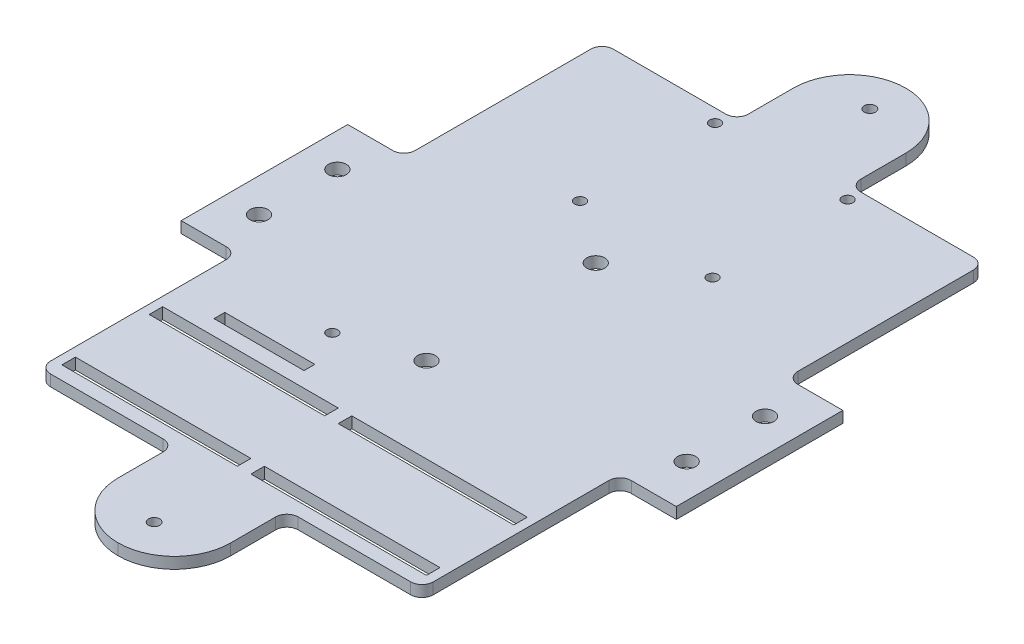
SolidWorks part; units mm, degrees
ref_plane "Front Plane" through (0, 0, 0) normal (0, 0, 1) x (1, 0, 0)
ref_plane "Top Plane" through (0, 0, 0) normal (0, 1, 0) x (1, 0, 0)
ref_plane "Right Plane" through (0, 0, 0) normal (1, 0, 0) x (0, 0, -1)
sketch "Sketch1" plane through (0, 0, 0) normal (0, 1, 0) x (1, 0, 0)
  line L0 (0, 102.87) -> (0, 158.75)
  line L1 (0, 0) -> (38.1, 0)
  line L2 (0, 0) -> (0, 55.88)
  line L3 (0, 158.75) -> (38.1, 158.75)
  line L4 (107.95, 0) -> (107.95, 55.88)
  line L5 (0, 102.87) -> (-15.875, 102.87)
  line L7 (0, 55.88) -> (-15.875, 55.88)
  line L8 (-15.875, 102.87) -> (-15.875, 55.88)
  line L9 (107.95, 102.87) -> (123.825, 102.87)
  line L11 (107.95, 55.88) -> (123.825, 55.88)
  line L12 (123.825, 102.87) -> (123.825, 55.88)
  line L14 (38.1, 158.75) -> (38.1, 190.5)
  line L15 (38.1, 190.5) -> (69.85, 190.5)
  line L16 (69.85, 158.75) -> (69.85, 190.5)
  line L18 (38.1, 0) -> (38.1, -31.75)
  line L19 (38.1, -31.75) -> (69.85, -31.75)
  line L20 (69.85, 0) -> (69.85, -31.75)
  line L21 (69.85, 158.75) -> (107.95, 158.75)
  line L22 (107.95, 102.87) -> (107.95, 158.75)
  line L23 (69.85, 0) -> (107.95, 0)
  dimension "D1" = 46.99
  dimension "D2" = 15.875
  dimension "D3" = 55.88
  dimension "D4" = 31.75
  dimension "D5" = 31.75
  dimension "D6" = 139.7
extrude "Boss-Extrude1" add sketch "Sketch1" along normal blind 3.175
fillet "Fillet1" radius 3.175 12 edges at (0, 1.5875, -55.88) (0, 1.5875, 0) (38.1, 1.5875, 0) (69.85, 1.5875, 0) (107.95, 1.5875, 0) (107.95, 1.5875, -55.88) (107.95, 1.5875, -102.87) (107.95, 1.5875, -158.75) (69.85, 1.5875, -158.75) (38.1, 1.5875, -158.75) (0, 1.5875, -158.75) (0, 1.5875, -102.87)
fillet "Fillet2" radius 15.875 4 edges at (38.1, 1.5875, 31.75) (69.85, 1.5875, 31.75) (69.85, 1.5875, -190.5) (38.1, 1.5875, -190.5)
sketch "Sketch2" plane through (0, 3.175, 0) normal (0, 1, 0) x (1, 0, 0)
  circle A0 centre (53.975, 180.34) radius 1.5875
  circle A1 centre (53.975, -21.59) radius 1.5875
  dimension "D1" = 3.175
  dimension "D2" = 10.16
  dimension "D3" = 10.16
extrude "Cut-Extrude1" cut sketch "Sketch2" against normal through all
sketch "Sketch3" plane through (0, 0, 0) normal (0, -1, 0) x (1, 0, 0)
  line L0 (-15.875, -55.88) -> (-3.175, -55.88) construction
  line L1 (-15.875, -102.87) -> (-15.875, -55.88) construction
  line L2 (-3.175, -102.87) -> (-15.875, -102.87) construction
  line L3 (111.125, -55.88) -> (123.825, -55.88) construction
  line L4 (123.825, -55.88) -> (123.825, -102.87) construction
  line L5 (123.825, -102.87) -> (111.125, -102.87) construction
  circle A0 centre (-6.35, -68.326) radius 2.5273
  circle A1 centre (-6.35, -90.424) radius 2.5273
  circle A2 centre (114.3, -68.326) radius 2.5273
  circle A3 centre (114.3, -90.424) radius 2.5273
  dimension "D1" = 5.0546
  dimension "D4" = 5.0546
  dimension "D7" = 5.0546
  dimension "D10" = 5.0546
  dimension "D2" = 12.446
  dimension "D3" = 9.525
  dimension "D5" = 12.446
  dimension "D6" = 9.525
  dimension "D8" = 12.446
  dimension "D9" = 9.525
  dimension "D11" = 9.525
  dimension "D12" = 12.446
extrude "Cut-Extrude2" cut sketch "Sketch3" against normal through all
sketch "Sketch4" plane through (0, 0, 0) normal (0, -1, 0) x (1, 0, 0)
  line L0 (107.95, -3.175) -> (107.95, -52.705) construction
  line L1 (73.025, 0) -> (104.775, 0) construction
  line L2 (107.95, -106.045) -> (107.95, -155.575) construction
  line L3 (34.925, -158.75) -> (3.175, -158.75) construction
  circle A0 centre (52.959, -56.261) radius 2.5273
  circle A1 centre (52.959, -104.013) radius 2.5273
  dimension "D1" = 5.0546
  dimension "D4" = 5.0546
  dimension "D2" = 54.991
  dimension "D3" = 56.261
  dimension "D5" = 54.991
  dimension "D6" = 54.737
extrude "Cut-Extrude3" cut sketch "Sketch4" against normal through all
sketch "Sketch6" plane through (0, 0, 0) normal (0, -1, 0) x (1, 0, 0)
  line L0 (3.175, 0) -> (34.925, 0) construction
  line L1 (0, -52.705) -> (0, -3.175) construction
  line L2 (107.95, -3.175) -> (107.95, -52.705) construction
  line L3 (73.025, 0) -> (104.775, 0) construction
  circle A0 centre (4.6977, -6.3716) radius 1.524
  circle A1 centre (51.1975, -6.3716) radius 1.524
  circle A2 centre (4.6977, -30.8724) radius 1.524
  circle A3 centre (51.1975, -30.8724) radius 1.524
  circle A4 centre (103.2523, -6.3716) radius 1.524
  circle A5 centre (56.7525, -6.3716) radius 1.524
  circle A6 centre (103.2523, -30.8724) radius 1.524
  circle A7 centre (56.7525, -30.8724) radius 1.524
  dimension "D1" = 3.048
  dimension "D4" = 3.048
  dimension "D7" = 3.048
  dimension "D10" = 3.048
  dimension "D13" = 3.048
  dimension "D16" = 3.048
  dimension "D19" = 3.048
  dimension "D22" = 3.048
  dimension "D2" = 6.3716
  dimension "D3" = 4.6977
  dimension "D5" = 6.3716
  dimension "D6" = 51.1975
  dimension "D8" = 4.6977
  dimension "D9" = 30.8724
  dimension "D11" = 51.1975
  dimension "D12" = 30.8724
  dimension "D14" = 4.6977
  dimension "D15" = 6.3716
  dimension "D17" = 6.3716
  dimension "D18" = 51.1975
  dimension "D20" = 4.6977
  dimension "D21" = 30.8724
  dimension "D23" = 51.1975
  dimension "D24" = 30.8724
extrude "Cut-Extrude5" [suppressed] cut sketch "Sketch6" against normal through all
sketch "Sketch9" [suppressed] plane through (0, 0, 0) normal (0, -1, 0) x (1, 0, 0)
  line L0 (3.175, 0) -> (34.925, 0) construction
  line L1 (6.6027, -4.064) -> (46.1175, -4.064)
  line L2 (6.6027, -4.064) -> (6.6027, -8.636)
  line L3 (6.6027, -8.636) -> (46.1175, -8.636)
  line L4 (46.1175, -4.064) -> (46.1175, -8.636)
  line L5 (73.025, 0) -> (104.775, 0) construction
  line L6 (61.8325, -4.064) -> (101.3473, -4.064)
  line L7 (61.8325, -4.064) -> (61.8325, -8.636)
  line L8 (61.8325, -8.636) -> (101.3473, -8.636)
  line L9 (101.3473, -4.064) -> (101.3473, -8.636)
  line L11 (6.6027, -28.702) -> (46.1175, -28.702)
  line L12 (6.6027, -28.702) -> (6.6027, -33.274)
  line L13 (6.6027, -33.274) -> (46.1175, -33.274)
  line L14 (46.1175, -28.702) -> (46.1175, -33.274)
  line L15 (61.8325, -28.702) -> (101.3473, -28.702)
  line L16 (61.8325, -28.702) -> (61.8325, -33.274)
  line L17 (61.8325, -33.274) -> (101.3473, -33.274)
  line L18 (101.3473, -28.702) -> (101.3473, -33.274)
  circle A0 centre (51.1975, -6.3716) radius 1.524 construction
  circle A1 centre (4.6977, -6.3716) radius 1.524 construction
  circle A2 centre (56.7525, -6.3716) radius 1.524 construction
  circle A3 centre (103.2523, -6.3716) radius 1.524 construction
  circle A4 centre (4.6977, -30.8724) radius 1.524 construction
  circle A5 centre (51.1975, -30.8724) radius 1.524 construction
  circle A6 centre (103.2523, -30.8724) radius 1.524 construction
  circle A7 centre (56.7525, -30.8724) radius 1.524 construction
  dimension "D1" = 4.572
  dimension "D2" = 5.08
  dimension "D3" = 1.905
  dimension "D4" = 4.064
  dimension "D5" = 5.08
  dimension "D6" = 1.905
  dimension "D7" = 4.064
  dimension "D8" = 4.572
  dimension "D9" = 1.905
  dimension "D10" = 5.08
  dimension "D11" = 28.702
  dimension "D12" = 4.572
  dimension "D13" = 1.905
  dimension "D14" = 5.08
  dimension "D15" = 28.702
  dimension "D16" = 4.572
extrude "Cut-Extrude8" [suppressed] cut sketch "Sketch9" against normal through all
sketch "Sketch7" plane through (0, 0, 0) normal (0, -1, 0) x (1, 0, 0)
  line L0 (3.175, 0) -> (34.925, 0) construction
  line L1 (0, -52.705) -> (0, -3.175) construction
  circle A0 centre (32.8714, -49.784) radius 1.524
  dimension "D1" = 3.048
  dimension "D2" = 49.784
  dimension "D3" = 32.8714
extrude "Cut-Extrude6" cut sketch "Sketch7" against normal through all
sketch "Sketch8" plane through (0, 0, 0) normal (0, -1, 0) x (1, 0, 0)
  line L0 (0, -155.575) -> (0, -106.045) construction
  line L1 (34.925, -158.75) -> (3.175, -158.75) construction
  line L2 (104.775, -158.75) -> (73.025, -158.75) construction
  line L3 (107.95, -106.045) -> (107.95, -155.575) construction
  circle A0 centre (35.6006, -116.9416) radius 1.524
  circle A1 centre (35.6006, -155.0416) radius 1.524
  circle A2 centre (72.9996, -116.9416) radius 1.524
  circle A3 centre (72.9996, -155.0416) radius 1.524
  dimension "D1" = 3.048
  dimension "D4" = 3.048
  dimension "D7" = 3.048
  dimension "D10" = 3.048
  dimension "D2" = 35.6006
  dimension "D3" = 41.8084
  dimension "D5" = 3.7084
  dimension "D6" = 35.6006
  dimension "D8" = 41.8084
  dimension "D9" = 34.9504
  dimension "D11" = 34.9504
  dimension "D12" = 3.7084
extrude "Cut-Extrude7" cut sketch "Sketch8" against normal through all
sketch "Sketch10" plane through (0, 0, 0) normal (0, -1, 0) x (1, 0, 0)
  line L0 (0, -52.705) -> (0, -3.175) construction
  line L1 (12.7, -36.576) -> (38.1, -36.576)
  line L2 (12.7, -36.576) -> (12.7, -39.624)
  line L3 (12.7, -39.624) -> (38.1, -39.624)
  line L4 (38.1, -36.576) -> (38.1, -39.624)
  circle A0 centre (32.8714, -49.784) radius 1.524 construction
  dimension "D1" = 10.16
  dimension "D2" = 3.048
  dimension "D3" = 25.4
  dimension "D4" = 12.7
extrude "Cut-Extrude9" cut sketch "Sketch10" against normal through all
sketch "Sketch11" plane through (0, 0, 0) normal (0, -1, 0) x (1, 0, 0)
  line L0 (3.175, 0) -> (34.925, 0) construction
  line L1 (2.54, -3.81) -> (52.07, -3.81)
  line L2 (2.54, -3.81) -> (2.54, -7.62)
  line L3 (2.54, -7.62) -> (52.07, -7.62)
  line L4 (52.07, -3.81) -> (52.07, -7.62)
  line L5 (0, -52.705) -> (0, -3.175) construction
  line L6 (73.025, 0) -> (104.775, 0) construction
  line L7 (2.54, -28.448) -> (52.07, -28.448)
  line L8 (2.54, -28.448) -> (2.54, -32.258)
  line L9 (2.54, -32.258) -> (52.07, -32.258)
  line L10 (52.07, -28.448) -> (52.07, -32.258)
  line L11 (55.88, -3.81) -> (105.41, -3.81)
  line L12 (55.88, -3.81) -> (55.88, -7.62)
  line L13 (55.88, -7.62) -> (105.41, -7.62)
  line L14 (105.41, -3.81) -> (105.41, -7.62)
  line L15 (107.95, -3.175) -> (107.95, -52.705) construction
  line L17 (55.88, -28.448) -> (105.41, -28.448)
  line L18 (55.88, -28.448) -> (55.88, -32.258)
  line L19 (55.88, -32.258) -> (105.41, -32.258)
  line L20 (105.41, -28.448) -> (105.41, -32.258)
  dimension "D1" = 3.81
  dimension "D2" = 2.54
  dimension "D3" = 49.53
  dimension "D4" = 3.81
  dimension "D5" = 49.53
  dimension "D6" = 3.81
  dimension "D7" = 2.54
  dimension "D8" = 28.448
  dimension "D9" = 49.53
  dimension "D10" = 3.81
  dimension "D11" = 2.54
  dimension "D12" = 3.81
  dimension "D13" = 2.54
  dimension "D14" = 3.81
  dimension "D15" = 49.53
  dimension "D16" = 28.448
extrude "Cut-Extrude10" cut sketch "Sketch11" against normal through all
